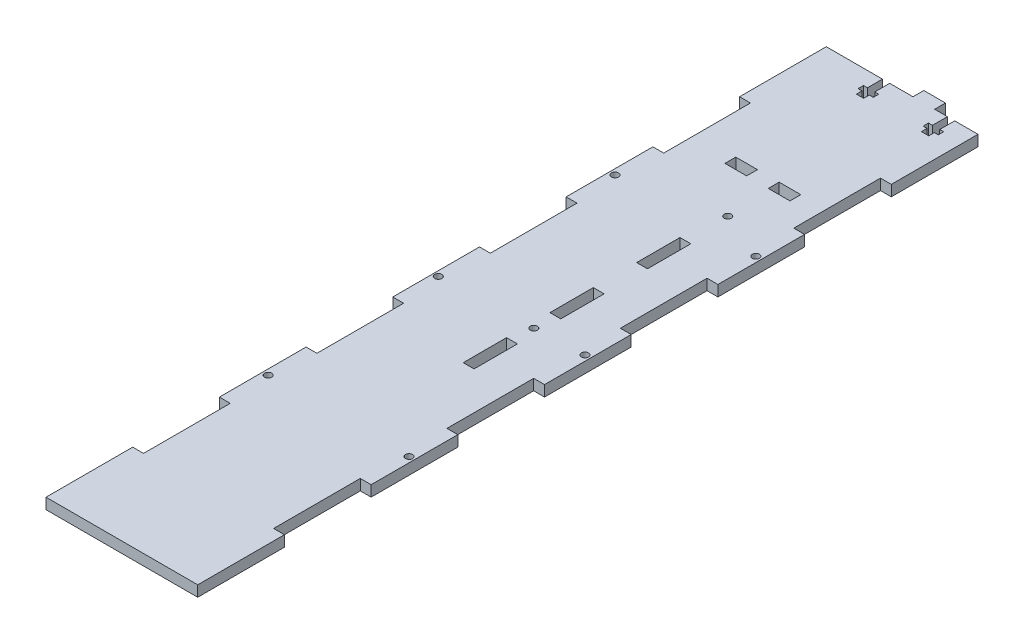
SolidWorks part; units mm, degrees
material "Pine"
ref_plane "Front Plane" through (0, 0, 0) normal (0, 0, 1) x (1, 0, 0)
ref_plane "Top Plane" through (0, 0, 0) normal (0, 1, 0) x (1, 0, 0)
ref_plane "Right Plane" through (0, 0, 0) normal (1, 0, 0) x (0, 0, -1)
sketch "Sketch1" plane through (0, 0, 0) normal (0, 0, 1) x (1, 0, 0)
  line L1 (38.1, -38.1) -> (-38.1, -38.1) construction
  line L2 (38.1, -38.1) -> (38.1, 38.1) construction
  line L3 (38.1, 38.1) -> (-38.1, 38.1)
  line L4 (-38.1, -38.1) -> (-38.1, 38.1) construction
  line L5 (38.1, -38.1) -> (-38.1, 38.1) construction
  line L6 (38.1, 38.1) -> (-38.1, -38.1) construction
  line L7 (-38.1, 38.1) -> (38.1, 38.1)
  line L8 (-38.1, 38.1) -> (-38.1, 44.45)
  line L9 (-38.1, 44.45) -> (38.1, 44.45)
  line L10 (38.1, 38.1) -> (38.1, 44.45)
  point P0 (0, 0)
  dimension "D1" = 76.2
  dimension "D2" = 6.35
extrude "Base Extrusion" add sketch "Sketch1" along normal blind 457.2 contours L3 L10 L9 L8 region at (0, 41.275, 0)
sketch "Sketch2" plane through (0, 44.45, 0) normal (0, 1, 0) x (1, 0, 0)
  line L0 (-44.45, -406.4) -> (-44.45, -355.6) construction
  line L1 (-38.1, -457.2) -> (-44.45, -457.2)
  line L2 (-38.1, -457.2) -> (-38.1, -406.4)
  line L3 (-38.1, -406.4) -> (-44.45, -406.4)
  line L4 (-44.45, -457.2) -> (-44.45, -406.4)
  line L5 (-44.45, -457.2) -> (-44.45, 0) construction
  line L6 (-44.45, -355.6) -> (-44.45, -304.8) construction
  line L7 (-44.45, -304.8) -> (-44.45, -254) construction
  line L8 (-44.45, -254) -> (-44.45, -203.2) construction
  line L9 (-44.45, -203.2) -> (-44.45, -152.4) construction
  line L10 (-44.45, -152.4) -> (-44.45, -101.6) construction
  line L11 (-44.45, -101.6) -> (-44.45, -50.8) construction
  line L12 (-44.45, -50.8) -> (-44.45, 0) construction
  dimension "D1" = 6.35
extrude "Tab" add sketch "Sketch2" against normal up to surface (6.35 mm away) up to face at (0, 38.1, 228.6)
pattern_linear "LPattern1" count 5 spacing 101.6 along (0, 0, -1) of "Tab"
mirror "Mirror2" about plane through (0, 0, 0) normal (1, 0, 0) of "LPattern1"
sketch "Sketch3" plane through (0, 38.1, 0) normal (0, -1, 0) x (-1, 0, 0)
  line L1 (-23.1736, -82.55) -> (-10.4736, -82.55)
  line L2 (-23.1736, -82.55) -> (-23.1736, -88.9)
  line L3 (-23.1736, -88.9) -> (-10.4736, -88.9)
  line L4 (-10.4736, -82.55) -> (-10.4736, -88.9)
  line L5 (2.2264, -82.55) -> (14.9264, -82.55)
  line L6 (2.2264, -82.55) -> (2.2264, -88.9)
  line L7 (2.2264, -88.9) -> (14.9264, -88.9)
  line L8 (14.9264, -82.55) -> (14.9264, -88.9)
extrude "Cut-Extrude1" cut sketch "Sketch3" against normal through all
sketch "Sketch4" plane through (0, 0, 0) normal (0, 0, -1) x (-1, 0, 0)
  line L0 (44.45, 44.45) -> (-44.45, 44.45) construction
  line L1 (-6.35, 44.45) -> (-19.05, 44.45)
  line L2 (-6.35, 44.45) -> (-6.35, 38.1)
  line L3 (-6.35, 38.1) -> (-19.05, 38.1)
  line L4 (-19.05, 44.45) -> (-19.05, 38.1)
  line L5 (-44.45, 38.1) -> (44.45, 38.1) construction
  dimension "D1" = 25.4
  dimension "D2" = 12.7
extrude "Boss-Extrude1" add sketch "Sketch4" along normal blind 6.35
sketch "Sketch5" plane through (0, 38.1, 0) normal (0, -1, 0) x (1, 0, 0)
  line L1 (9.525, 241.3) -> (15.875, 241.3)
  line L2 (9.525, 241.3) -> (9.525, 266.7)
  line L3 (9.525, 266.7) -> (15.875, 266.7)
  line L4 (15.875, 241.3) -> (15.875, 266.7)
  line L5 (9.525, 215.9) -> (15.875, 215.9)
  line L6 (9.525, 215.9) -> (9.525, 190.5)
  line L7 (9.525, 190.5) -> (15.875, 190.5)
  line L8 (15.875, 215.9) -> (15.875, 190.5)
  line L9 (9.525, 165.1) -> (15.875, 165.1)
  line L10 (9.525, 165.1) -> (9.525, 139.7)
  line L11 (9.525, 139.7) -> (15.875, 139.7)
  line L12 (15.875, 165.1) -> (15.875, 139.7)
extrude "Cut-Extrude2" cut sketch "Sketch5" against normal blind 6.35
sketch "Sketch6" plane through (0, 44.45, 0) normal (0, 1, 0) x (1, 0, 0)
  line L0 (9.525, -230.6506) -> (15.875, -226.3834) construction
  line L1 (15.875, -230.6506) -> (9.525, -226.3834) construction
  line L2 (15.875, -117.0138) -> (9.525, -112.7466) construction
  line L3 (15.875, -112.7466) -> (9.525, -117.0138) construction
  circle A0 centre (12.7, -228.517) radius 2.0955
  circle A1 centre (12.7, -114.8802) radius 2.0955
  dimension "D1" = 4.191
  dimension "D2" = 4.191
extrude "Cut-Extrude3" cut sketch "Sketch6" against normal blind 6.35
sketch "Sketch7" plane through (0, 38.1, 0) normal (0, -1, 0) x (1, 0, 0)
  line L0 (6.35, 0) -> (-44.45, 0) construction
  line L1 (44.45, 0) -> (19.05, 0) construction
  line L2 (-9.4177, 0) -> (-9.4177, 16.4412) construction
  line L3 (28.6657, 0) -> (28.6657, 18.7421) construction
  line B0 (-11.5513, 0) -> (-7.2841, 0)
  line B1 (-7.2841, 11.938) -> (-4.9727, 11.938)
  line B2 (-4.9727, 11.938) -> (-4.9727, 8.763)
  line B3 (-4.9727, 8.763) -> (-7.2841, 8.763)
  line B4 (-7.2841, 8.763) -> (-7.2841, 0)
  line B5 (-7.2841, 11.938) -> (-7.2841, 15.24)
  line B6 (-7.2841, 15.24) -> (-11.5513, 15.24)
  line B7 (-11.5513, 11.938) -> (-11.5513, 15.24)
  line B8 (-11.5513, 8.763) -> (-11.5513, 0)
  line B9 (-13.8627, 8.763) -> (-11.5513, 8.763)
  line B10 (-13.8627, 11.938) -> (-13.8627, 8.763)
  line B11 (-11.5513, 11.938) -> (-13.8627, 11.938)
  line B12 (26.5321, 0) -> (30.7993, 0)
  line B13 (30.7993, 11.938) -> (33.1107, 11.938)
  line B14 (33.1107, 11.938) -> (33.1107, 8.763)
  line B15 (33.1107, 8.763) -> (30.7993, 8.763)
  line B16 (30.7993, 8.763) -> (30.7993, 0)
  line B17 (30.7993, 11.938) -> (30.7993, 15.24)
  line B18 (30.7993, 15.24) -> (26.5321, 15.24)
  line B19 (26.5321, 11.938) -> (26.5321, 15.24)
  line B20 (26.5321, 8.763) -> (26.5321, 0)
  line B21 (24.2207, 8.763) -> (26.5321, 8.763)
  line B22 (24.2207, 11.938) -> (24.2207, 8.763)
  line B23 (26.5321, 11.938) -> (24.2207, 11.938)
sketch_block_instance "TSlot-1"
sketch_block "TSlot" parameters "D1"=3.302, "D2"=3.175
sketch_block_instance "TSlot-4"
extrude "Cut-Extrude4" cut sketch "Sketch7" against normal blind 6.35
sketch "Sketch10" plane through (0, 38.1, 0) normal (0, -1, 0) x (-1, 0, 0)
  line L0 (38.1, -332.3336) -> (44.45, -328.0664) construction
  line L2 (44.45, -304.8) -> (44.45, -355.6) construction
  line L3 (-38.1, -332.3336) -> (-44.45, -328.0664) construction
  line L4 (-44.45, -304.8) -> (-44.45, -355.6) construction
  line L5 (-38.1, -328.0664) -> (-44.45, -332.3336) construction
  line L6 (-38.1, -229.2703) -> (-44.45, -225.0031) construction
  line L7 (-44.45, -203.2) -> (-44.45, -254) construction
  line L8 (-38.1, -225.0031) -> (-44.45, -229.2703) construction
  line L9 (38.1, -232.1969) -> (44.45, -228.6) construction
  line L10 (44.45, -203.2) -> (44.45, -254) construction
  line L11 (38.6413, -228.2934) -> (44.45, -232.1969) construction
  line L12 (-38.1, -129.1336) -> (-44.45, -124.8664) construction
  line L13 (-44.45, -101.6) -> (-44.45, -152.4) construction
  line L14 (-38.1, -124.8664) -> (-44.45, -129.1336) construction
  line L15 (38.1, -129.1336) -> (44.45, -124.8664) construction
  line L16 (44.45, -101.6) -> (44.45, -152.4) construction
  line L17 (38.1, -124.8664) -> (44.45, -129.1336) construction
  line L18 (38.1, -328.0664) -> (44.45, -332.3336) construction
  circle A0 centre (41.275, -127) radius 2.0955
  circle A1 centre (-41.275, -127) radius 2.0955
  circle A2 centre (-41.275, -227.1367) radius 2.0955
  circle A3 centre (41.5456, -230.2452) radius 2.0955
  circle A4 centre (-41.275, -330.2) radius 2.0955
  circle A5 centre (41.275, -330.2) radius 2.0955
  dimension "D1" = 4.191
extrude "Cut-Extrude5" cut sketch "Sketch10" against normal blind 6.35
